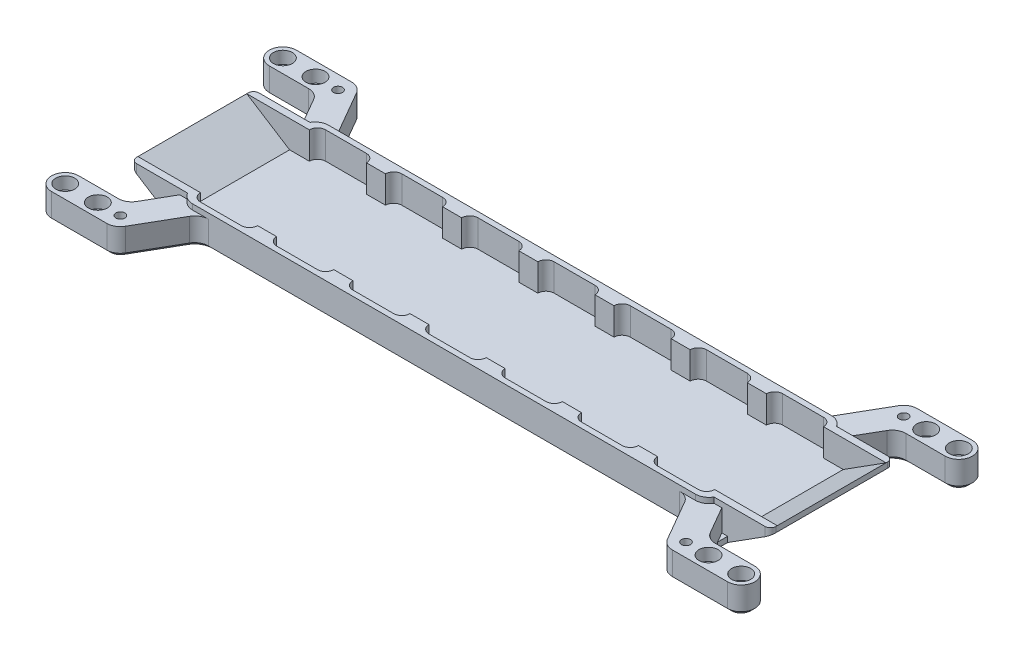
SolidWorks part; units mm, degrees
material "ABS"
ref_plane "前视基准面" through (0, 0, 0) normal (0, 0, 1) x (1, 0, 0)
ref_plane "上视基准面" through (0, 0, 0) normal (0, 1, 0) x (1, 0, 0)
ref_plane "右视基准面" through (0, 0, 0) normal (1, 0, 0) x (0, 0, -1)
sketch "草图1" plane through (0, 0, 0) normal (0, 1, 0) x (1, 0, 0)
  line L0 (-14.275, 0) -> (14.275, 0) construction
  line L1 (-14.275, 5) -> (14.275, 5)
  line L2 (-14.275, -5) -> (14.275, -5)
  line L3 (14.275, 0) -> (25.822, -20) construction
  line L4 (25.822, -20) -> (210.628, -20) construction
  line L5 (14.275, 0) -> (25.822, -20) construction
  line L6 (18.6051, 2.5) -> (30.1521, -17.5)
  line L7 (9.9449, -2.5) -> (21.4919, -22.5)
  line L8 (25.822, -20) -> (210.628, -20) construction
  line L9 (25.822, -15) -> (210.628, -15)
  line L10 (25.822, -25) -> (210.628, -25)
  line L11 (210.628, -20) -> (222.175, 0) construction
  line L12 (206.2979, -17.5) -> (217.8449, 2.5)
  line L13 (214.9581, -22.5) -> (226.5051, -2.5)
  line L14 (222.175, 0) -> (250.725, 0) construction
  line L15 (222.175, 5) -> (250.725, 5)
  line L16 (222.175, -5) -> (250.725, -5)
  circle A0 centre (-14.275, 0) radius 1.65
  arc A1 (-14.275, 5) -> (-14.275, -5) centre (-14.275, 0) ccw
  arc A2 (14.275, -5) -> (14.275, 5) centre (14.275, 0) ccw
  arc A3 (18.6051, 2.5) -> (9.9449, -2.5) centre (14.275, 0) ccw
  arc A4 (21.4919, -22.5) -> (30.1521, -17.5) centre (25.822, -20) ccw
  arc A5 (25.822, -15) -> (25.822, -25) centre (25.822, -20) ccw
  arc A6 (210.628, -25) -> (210.628, -15) centre (210.628, -20) ccw
  circle A7 centre (14.275, 0) radius 1.65
  arc A8 (206.2979, -17.5) -> (214.9581, -22.5) centre (210.628, -20) ccw
  arc A9 (226.5051, -2.5) -> (217.8449, 2.5) centre (222.175, 0) ccw
  arc A10 (222.175, 5) -> (222.175, -5) centre (222.175, 0) ccw
  arc A11 (250.725, -5) -> (250.725, 5) centre (250.725, 0) ccw
  circle A12 centre (250.725, 0) radius 1.65
  circle A13 centre (222.175, 0) radius 1.65
  point P2 (0, 0)
  point P12 (20.0485, -10)
  point P18 (118.225, -20)
  point P27 (216.4015, -10)
  point P34 (236.45, 0)
  dimension "D1" = 3.3
  dimension "D2" = 5
  dimension "D7" = 3.3
  dimension "D11" = 3.3
  dimension "D12" = 3.3
  dimension "D3" = 28.55
  dimension "D4" = 20
  dimension "D5" = 120
  dimension "D6" = 120
  dimension "D8" = 20
  dimension "D9" = 28.55
  dimension "D10" = 207.9
extrude "凸台-拉伸1" add sketch "草图1" along normal blind 12 contours A3 L1 A1 L2 L7 A0 | A2 A3 L7 L2 | A5 L9 L6 A2 L2 L7 | L9 A5 A4 L6 | L10 A6 L9 L6 A4 | A10 L12 L9 A6 L13 L16 | L12 A8 A6 L9 | A9 A10 L16 L13 A13 | L16 A11 L15 A9 L13 A12 region at (-3.682, 0, -0.0218) region at (16.7043, 0, -4.2077) region at (20.0485, 0, 10) region at (118.225, 0, 20.0068) region at (25.8655, 0, 19.9247) region at (216.4015, 0, 10) region at (210.5845, 0, 19.9247) region at (219.7457, 0, -4.2077) region at (240.132, 0, -0.0218)
fillet "圆角1" radius 5 4 edges at (11.3882, 6, 5) (225.0618, 6, 5) (207.7412, 6, 15) (28.7088, 6, 15)
sketch "草图3" plane through (0, 0, 0) normal (0, 1, 0) x (1, 0, 0)
  circle A0 centre (-14.275, 0) radius 2.75
  circle A1 centre (14.275, 0) radius 3
  circle A2 centre (14.275, 0) radius 1.65 construction
  circle A3 centre (-14.275, 0) radius 1.65 construction
  circle A4 centre (250.725, 0) radius 2.75
  circle A5 centre (222.175, 0) radius 3
  circle A6 centre (222.175, 0) radius 1.65 construction
  circle A7 centre (250.725, 0) radius 1.65 construction
  dimension "D1" = 6
  dimension "D2" = 5.5
  dimension "D3" = 6
  dimension "D4" = 5.5
extrude "切除-拉伸1" cut sketch "草图3" along normal blind 3
sketch "草图4" plane through (0, 12, 0) normal (0, 1, 0) x (1, 0, 0)
  line L0 (25.822, -25) -> (210.628, -25) construction
  line L1 (-49.5799, -15) -> (304.1802, -15)
  line L2 (-49.5799, -15) -> (-49.5799, 56.9164)
  line L3 (-49.5799, 56.9164) -> (304.1802, 56.9164)
  line L4 (304.1802, -15) -> (304.1802, 56.9164)
  dimension "D1" = 10
extrude "切除-拉伸2" cut sketch "草图4" against normal blind 2
fillet "圆角2" radius 5 2 edges at (17.1618, 11, 15) (219.2882, 11, 15)
sketch "草图5" plane through (0, 12, 0) normal (0, 1, 0) x (1, 0, 0)
  line L0 (110.725, -20) -> (125.725, -20) construction
  line L1 (110.725, -17) -> (125.725, -17)
  line L2 (110.725, -23) -> (125.725, -23)
  line L3 (118.225, -20) -> (118.225, -15) construction
  line L4 (25.822, -15) -> (210.628, -15) construction
  arc A0 (110.725, -17) -> (110.725, -23) centre (110.725, -20) ccw
  arc A1 (125.725, -23) -> (125.725, -17) centre (125.725, -20) ccw
  point P2 (118.225, -20)
  dimension "D2" = 3
  dimension "D1" = 5
  dimension "D3" = 15
extrude "切除-拉伸3" cut sketch "草图5" against normal blind 10
pattern_linear "阵列(线性)1" count 4 spacing 28 along (1, 0, 0) count 4 spacing 28 along (-1, 0, 0) of "切除-拉伸3"
sketch "草图6" plane through (0, 10, 0) normal (0, 1, 0) x (1, 0, 0)
  circle A0 centre (-6, 0) radius 3.5
  circle A1 centre (6, 0) radius 3.5
  circle A2 centre (230.455, 0) radius 3.5
  circle A3 centre (242.445, 0) radius 3.5
  circle A4 centre (250.725, 0) radius 1.65 construction
  circle A5 centre (222.175, 0) radius 1.65 construction
  dimension "D1" = 7
  dimension "D2" = 7
  dimension "D3" = 6
  dimension "D4" = 6
  dimension "D5" = 7
  dimension "D6" = 7
  dimension "D7" = 8.28
  dimension "D8" = 8.28
extrude "切除-拉伸4" cut sketch "草图6" against normal blind 4.5
sketch "草图7" plane through (0, 5.5, 0) normal (0, 1, 0) x (1, 0, 0)
  circle A0 centre (-6, 0) radius 1.6
  circle A1 centre (6, 0) radius 1.6
  circle A2 centre (230.455, 0) radius 1.6
  circle A3 centre (242.445, 0) radius 1.6
  dimension "D1" = 3.2
  dimension "D2" = 3.2
  dimension "D3" = 3.2
  dimension "D4" = 3.2
extrude "切除-拉伸5" cut sketch "草图7" against normal blind 10
sketch "草图8" plane through (0, 0, 0) normal (0, -1, 0) x (-1, 0, 0)
  line L0 (-16.475, -13.8105) -> (-16.475, -40)
  line L1 (-16.475, -40) -> (-219.975, -40)
  line L2 (-219.975, -40) -> (-219.975, -13.8105)
  line L4 (-12.8316, -7.5) -> (-21.4919, -22.5) construction
  line L5 (-214.9581, -22.5) -> (-223.6184, -7.5) construction
  line L6 (-25.822, -25) -> (-210.628, -25) construction
  line L7 (-16.475, -13.8105) -> (-20.0485, -20)
  line L8 (-20.0485, -20) -> (-216.4015, -20)
  line L9 (-216.4015, -20) -> (-219.975, -13.8105)
  circle A0 centre (-222.175, 0) radius 1.65 construction
  circle A1 centre (-14.275, 0) radius 3 construction
  dimension "D2" = 2.2
  dimension "D4" = 2.2
  dimension "D1" = 15
  dimension "D3" = 5
extrude "凸台-拉伸2" add sketch "草图8" against normal blind 2
sketch "草图9" plane through (0, 12, 0) normal (0, 1, 0) x (1, 0, 0)
  line L1 (26.725, -20) -> (209.725, -20)
  line L6 (209.725, -20) -> (219.975, -20)
  line L7 (219.975, -13.8105) -> (219.975, -40) construction
  line L8 (219.975, -20) -> (219.975, -40)
  line L9 (219.975, -40) -> (16.475, -40)
  line L10 (16.475, -40) -> (16.475, -20)
  line L11 (16.475, -40) -> (16.475, -13.8105) construction
  line L12 (16.475, -20) -> (26.725, -20)
  arc A1 (209.725, -23) -> (209.725, -17) centre (209.725, -20) ccw construction
  arc A3 (26.725, -17) -> (26.725, -23) centre (26.725, -20) ccw construction
extrude "切除-拉伸6" cut sketch "草图9" against normal up to surface (10 mm away) up to face at (118.225, 2, 25.4727)
sketch "草图11" plane through (0, 0, 20) normal (0, 0, 1) x (1, 0, 0)
  line L2 (16.475, 12) -> (0.725, 12)
  line L3 (16.475, 12) -> (23.725, 12)
  line L4 (23.725, 12) -> (23.725, 0)
  line L5 (219.975, 0) -> (16.475, 0) construction
  line L6 (23.725, 0) -> (16.475, 0)
  line L7 (0.725, 12) -> (0.725, 10)
  line L8 (0.725, 10) -> (16.475, 0)
extrude "凸台-拉伸3" add sketch "草图11" against normal blind 2.5
sketch "草图12" plane through (0, 0, 20) normal (0, 0, 1) x (1, 0, 0)
  line L0 (16.475, 2) -> (0.725, 12)
  line L1 (0.725, 12) -> (0.725, 10)
  line L5 (16.475, 0) -> (16.475, 2)
  line L6 (0.725, 10) -> (16.475, 0)
extrude "凸台-拉伸4" add sketch "草图12" along direction (0, 0, -1) on the side of the normal up to surface (20 mm away) up to face at (118.225, 1, 40)
ref_point "点1"
ref_plane "基准面1" through (118.225, 0, 0) normal (-1, 0, 0) x (0, 0, 1)
mirror "镜向2" about plane through (118.225, 0, 0) normal (-1, 0, 0) of "凸台-拉伸4", "凸台-拉伸3"
mirror "镜向1" about plane through (16.475, 2, 40) normal (0, 0, 1) of bodies 121 115
sketch "草图10" plane through (0, 0, 0) normal (0, -1, 0) x (-1, 0, 0)
  line L0 (6, 5) -> (14.275, 5)
  line L1 (14.275, -5) -> (-8.5015, -5) construction
  line L4 (19.275, 0) -> (19.275, 5)
  line L5 (14.275, -85) -> (-14.275, -85) construction
  line L6 (6, -85) -> (23.3633, -85)
  line L7 (23.3633, -85) -> (23.3633, -75)
  line L8 (23.3633, -75) -> (6, -75)
  line L9 (-242.445, -85) -> (-259.3044, -85)
  line L10 (-259.3044, -85) -> (-259.3044, -75)
  line L11 (-259.3044, -75) -> (-242.445, -75)
  line L12 (-242.445, -5) -> (-258.7417, -5)
  line L13 (-258.7417, -5) -> (-258.7417, 5)
  line L14 (-258.7417, 5) -> (-242.445, 5)
  line L15 (19.275, 5) -> (14.275, 5)
  line L16 (6, -5) -> (19.275, -5)
  line L17 (19.275, -5) -> (19.275, 0)
  circle A0 centre (6, 0) radius 5
  circle A1 centre (6, 0) radius 1.6 construction
  circle A2 centre (6, -80) radius 5
  circle A3 centre (6, -80) radius 1.6 construction
  circle A4 centre (-242.445, -80) radius 5
  circle A5 centre (-242.445, 0) radius 5
  circle A6 centre (6, 0) radius 5
  arc A7 (14.275, -5) -> (14.275, 5) centre (14.275, 0) ccw construction
extrude "切除-拉伸7" cut sketch "草图10" against normal blind 20 contours A0 | A5 L14 L13 L12 | A4 L11 L10 L9 | A2 L6 L7 L8 region at (-14.5344, 0, 0) region at (-16.5988, 0, 80) region at (252.7901, 0, 80) region at (252.5065, 0, 0)
fillet "圆角4" radius 2 4 edges at (235.725, 11, 62.5) (235.725, 11, 17.5) (0.725, 11, 17.5) (0.725, 11, 62.5)
chamfer "倒角1" distance 1.5 angle 45 34 edges at (14.6533, 0, 69.3447) (221.7967, 0, 69.3447) (11.0015, 0, 74.3301) (225.4485, 0, 74.3301) (1.2507, 0, 75) (235.1968, 0, 75) (-11, 0, 80) (247.445, 0, 80) (4.1375, 0, 85) (232.31, 0, 85) (16.775, 0, 84.3301) (219.675, 0, 84.3301) (22.9353, 0, 75) (213.5147, 0, 75) (29.0955, 0, 65.6699) (207.3545, 0, 65.6699) (118.225, 0, 65) (14.6533, 0, 10.6553) (221.7967, 0, 10.6553) (11.0015, 0, 5.6699) (225.4485, 0, 5.6699) (1.2507, 0, 5) (235.1968, 0, 5) (-11, 0, 0) (247.445, 0, 0) (4.1375, 0, -5) (232.31, 0, -5) (16.775, 0, -4.3301) (219.675, 0, -4.3301) (22.9353, 0, 5) (213.5147, 0, 5) (29.0955, 0, 14.3301) (207.3545, 0, 14.3301) (118.225, 0, 15)
